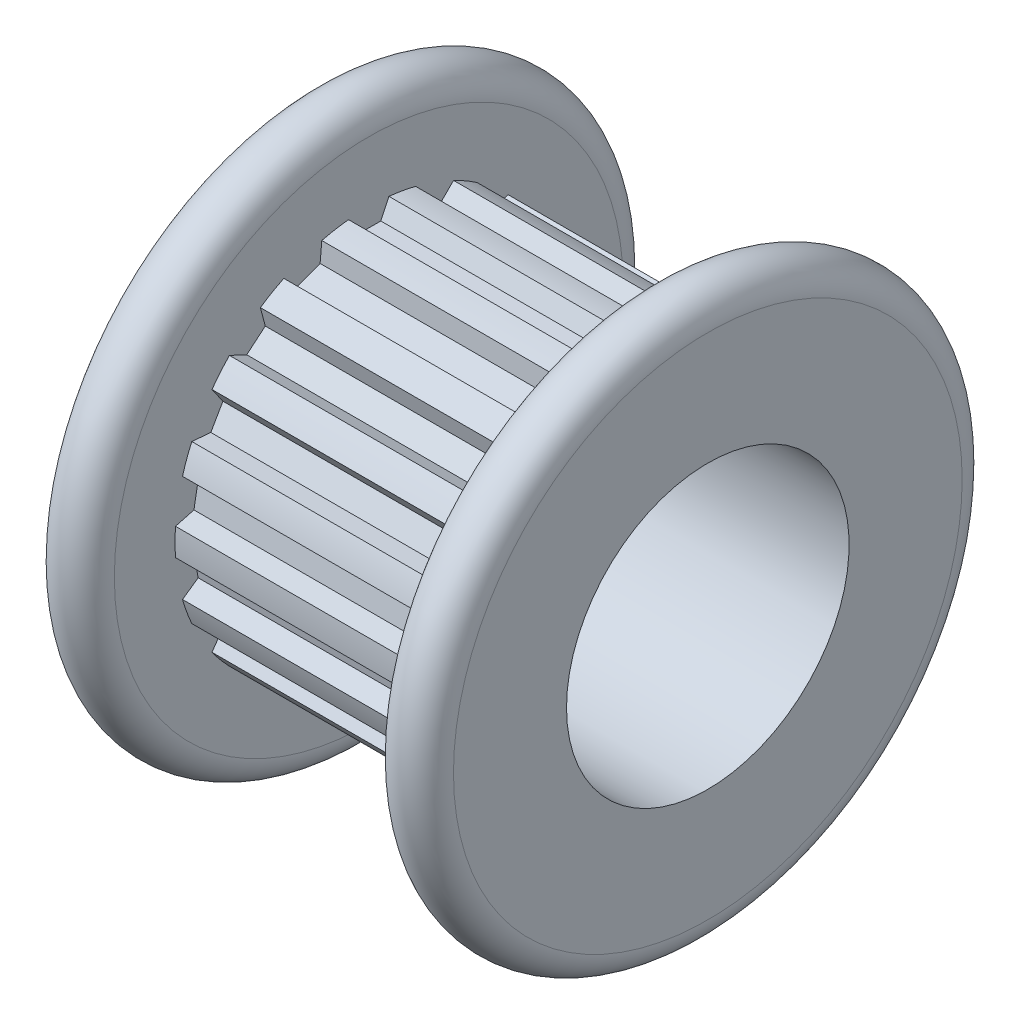
SolidWorks part; units mm, degrees
ref_plane "Front Plane" through (0, 0, 0) normal (0, 0, 1) x (1, 0, 0)
ref_plane "Top Plane" through (0, 0, 0) normal (0, 1, 0) x (1, 0, 0)
ref_plane "Right Plane" through (0, 0, 0) normal (1, 0, 0) x (0, 0, -1)
sketch "Sketch2" plane through (0, 0, 0) normal (1, 0, 0) x (0, 0, -1)
  line L3 (0, 0) -> (0, 4.9745) construction
  line L6 (0, -5.4825) -> (0, -5.8) construction
  line L7 (-0.5715, 5.4526) -> (-0.343, 4.9627)
  line L8 (0.5715, 5.4526) -> (0.343, 4.9627)
  line L9 (-0.5715, 5.4526) -> (-0.6423, 5.6046)
  line L10 (0.5715, 5.4526) -> (0.6423, 5.6046)
  line L12 (-0.343, 4.9627) -> (0.343, 4.9627)
  line L14 (0, 5.4825) -> (0, 5.8) construction
  line L15 (0, 0) -> (0, -1.143) construction
  circle A0 centre (0, 0) radius 5.8 construction
  circle A1 centre (0, 0) radius 4.9745 construction
  circle A2 centre (0, 0) radius 5.4825 construction
  arc A7 (0.6423, 5.6046) -> (-0.6423, 5.6046) centre (0, 0) ccw
  point P5 (0, 5.6412)
  dimension "D3" = 0.3175
  dimension "D1" = 50
sketch "Sketch1" plane through (0, 0, 0) normal (0, 0, 1) x (1, 0, 0)
  line L0 (-1.6, 0) -> (9.6, 0) construction
  line L1 (-1.6, 4) -> (9.6, 4)
  line L5 (8, 5.55) -> (0, 5.55)
  line L6 (0, 5.55) -> (0, 7.2)
  line L7 (-1.6, 7.2) -> (-1.6, 4)
  line L11 (8, 5.55) -> (8, 7.2)
  line L12 (9.6, 7.2) -> (9.6, 4)
  arc A0 (0, 7.2) -> (-1.6, 7.2) centre (-0.8, 7.2) ccw
  arc A1 (8, 7.2) -> (9.6, 7.2) centre (8.8, 7.2) cw
  dimension "For Shaft Dia." = 8
  dimension "D2" = 1.6
  dimension "Overall Width" = 11.2
  dimension "Inside Width" = 8
  dimension "OD" = 16
  dimension "Flange Dia." = 11.1
revolve "Revolve1" add sketch "Sketch1" angle 360 mid plane about L0
sketch "Sketch8" plane through (0, 0, 0) normal (0, 0, 1) x (1, 0, 0)
  line L1 (9.6, 8.75) -> (5.15, 8.75)
  line L2 (9.6, 8.75) -> (9.6, 1.55)
  line L3 (9.6, 1.55) -> (5.15, 1.55)
  line L4 (5.15, 8.75) -> (5.15, 1.55)
  line L5 (9.6, -7.2) -> (9.6, 7.2) construction
  line L6 (-1.6, 8.75) -> (2.85, 8.75)
  line L7 (-1.6, 8.75) -> (-1.6, 1.55)
  line L8 (-1.6, 1.55) -> (2.85, 1.55)
  line L9 (2.85, 8.75) -> (2.85, 1.55)
  line L10 (-1.6, 7.2) -> (-1.6, -7.2) construction
  line L11 (-1.6, 0) -> (9.6, 0) construction
  line L12 (2.85, 8.75) -> (5.15, 8.75) construction
  line L13 (4, 8.75) -> (4, 0) construction
  line L14 (8, 5.55) -> (0, 5.55) construction
  dimension "D1" = 2.3
  dimension "D2" = 17.5
  dimension "D3" = 4
revolve "Cut-Revolve1" [suppressed] cut sketch "Sketch8" angle 360 about L11
sketch "Sketch4" plane through (0, 0, 0) normal (1, 0, 0) x (0, 0, -1)
  circle A0 centre (0, 0) radius 5.4825
  circle A1 centre (0, 0) radius 5.4825 construction
  circle A2 centre (0, 0) radius 5.8
  circle A4 centre (0, 0) radius 5.8 construction
extrude "Cut-Extrude2" cut sketch "Sketch4" along normal up to surface (8 mm away) up to face at (8, 0, 5.55)
sketch "Sketch3" plane through (0, 0, 0) normal (1, 0, 0) x (0, 0, -1)
  line L2 (-0.5715, 5.4526) -> (-0.343, 4.9627) construction
  line L3 (-0.343, 4.9627) -> (0.343, 4.9627) construction
  line L4 (0.5715, 5.4526) -> (0.343, 4.9627) construction
  line L5 (-0.6423, 5.6046) -> (-0.343, 4.9627)
  line L6 (-0.343, 4.9627) -> (0.343, 4.9627)
  line L7 (0.6423, 5.6046) -> (0.343, 4.9627)
  arc A1 (0.6423, 5.6046) -> (-0.6423, 5.6046) centre (0, 0) ccw construction
  arc A2 (0.6423, 5.6046) -> (-0.6423, 5.6046) centre (0, 0) ccw
extrude "Cut-Extrude1" cut sketch "Sketch3" along normal up to surface (8 mm away) up to face at (8, 0, -5.4825)
pattern_circular "CirPattern1" count 18 over 360 about axis through (-1.6, 0, 0) along (-1, 0, 0) of "Cut-Extrude1"
sketch "Sketch5" plane through (0, 0, 0) normal (0, 0, 1) x (1, 0, 0)
  point P0 (8, 0)
ref_axis "Center Axis 1" through (9.6, 0, 0) along (-1, 0, 0)
ref_plane "Contact Plane 1" through (8, 0, 0) normal (-1, 0, 0) x (0, 0, 1)
ref_plane "Contact Plane 2" through (-1.6, 0, 0) normal (-1, 0, 0) x (0, 0, 1)
equation "\"D3@Sketch2\" = (\"hs@Sketch2\"-\"ht@Sketch2\")/2"
